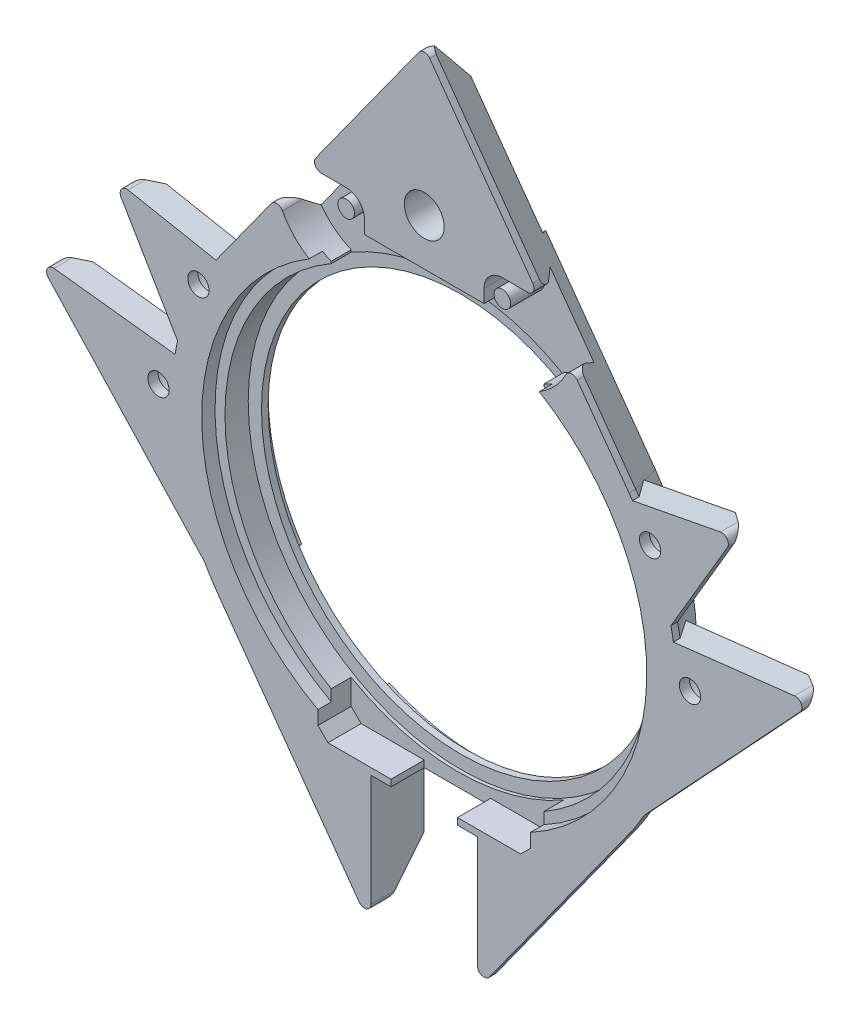
SolidWorks part; units mm, degrees
ref_plane "Спереди" through (0, 0, 0) normal (0, 0, 1) x (1, 0, 0)
ref_plane "Сверху" through (0, 0, 0) normal (0, 1, 0) x (1, 0, 0)
ref_plane "Справа" through (0, 0, 0) normal (1, 0, 0) x (0, 0, -1)
sketch "Эскиз1" plane through (0, 0, 0) normal (0, 0, 1) x (1, 0, 0)
  line L8 (0, 65) -> (30.8298, 22.2154)
  line L9 (0, -65) -> (30.8298, -22.2154)
  line L10 (-30.8298, 22.2154) -> (0, 65)
  line L11 (-30.8298, -22.2154) -> (0, -65)
  circle A0 centre (0, 0) radius 30
  arc A2 (30.8298, 22.2154) -> (30.8298, -22.2154) centre (0, 0) cw
  arc A3 (-30.8298, 22.2154) -> (-30.8298, -22.2154) centre (0, 0) ccw
  arc A10 (-0.8113, -63.8741) -> (0.8113, -63.8741) centre (0, -63.2895) ccw
  arc A11 (0.8113, 63.8741) -> (-0.8113, 63.8741) centre (0, 63.2895) ccw
  point P5 (0, -65)
  point P9 (0, 65)
  point P15 (0, 65)
  point P16 (0, -65)
  dimension "D1" = 60
  dimension "D2" = 2
  dimension "D7" = 38
  dimension "D8" = 65
  dimension "D9" = 65
extrude "Бобышка-Вытянуть1" add sketch "Эскиз1" along normal blind 8
chamfer "Фаска12" distance 7 distance2 5 6 edges at (-15.8206, -43.0447, 0) (15.8206, -43.0447, 0) (38, 0, 0) (-38, 0, 0) (-15.8206, 43.0447, 0) (15.8206, 43.0447, 0) first distance on face at (-15.8206, -43.0447, 4) first distance on face at (15.8206, -43.0447, 4) first distance on face at (34.4149, 0, 4) first distance on face at (-34.4149, 0, 4) first distance on face at (-15.8206, 43.0447, 4) first distance on face at (15.8206, 43.0447, 4)
sketch "Эскиз11" plane through (0, 0, 0) normal (0, 0, -1) x (-1, 0, 0)
  circle A0 centre (0, 0) radius 31.5
  circle A2 centre (0, 0) radius 30 construction
  dimension "D1" = 1.5
extrude "Вырез-Вытянуть1" cut sketch "Эскиз11" against normal blind 1.5
sketch "Эскиз17" plane through (0, 0, 8) normal (0, 0, -1) x (-1, 0, 0)
  line L0 (31.4303, -20.4545) -> (58.4303, 8.5455)
  line L1 (58.4303, 8.5455) -> (32.5307, 5.5455)
  line L3 (36.7549, 7.438) -> (46.7549, 24.438)
  line L4 (46.7549, 24.438) -> (25.9092, 20.438)
  line L5 (27.6586, -18) -> (31.4303, -20.4545)
  line L6 (36.7549, 7.438) -> (32.3444, 6.5455)
  line L7 (-32.3444, 6.5455) -> (-36.7549, 7.438)
  line L8 (-36.7549, 7.438) -> (-46.7549, 24.438)
  line L9 (-46.7549, 24.438) -> (-25.9092, 20.438)
  line L10 (-32.5307, 5.5455) -> (-58.4303, 8.5455)
  line L11 (-58.4303, 8.5455) -> (-31.4303, -20.4545)
  line L12 (-31.4303, -20.4545) -> (-27.6586, -18)
  arc A1 (-44.5835, 24.0214) -> (-45.6339, 22.5322) centre (-44.772, 23.0393) ccw
  circle A3 centre (0, 0) radius 33
  arc A6 (45.6339, 22.5322) -> (44.5835, 24.0214) centre (44.772, 23.0393) ccw
  arc A7 (56.5801, 6.5583) -> (55.7332, 8.233) centre (55.8482, 7.2397) ccw
  arc A8 (-55.7332, 8.233) -> (-56.5801, 6.5583) centre (-55.8482, 7.2397) ccw
  line M61 (0.8113, 63.8741) -> (30.8298, 22.2154)
  arc M62 (30.8298, 22.2154) -> (30.8298, -22.2154) centre (0, 0) cw
  line M64 (-0.8113, -63.8741) -> (-30.8298, -22.2154)
  arc M65 (-30.8298, -22.2154) -> (-30.8298, 22.2154) centre (0, 0) cw
  dimension "D11" = 66
  dimension "D3" = 2
  dimension "D2" = 18
  dimension "D8" = 1
  dimension "D12" = 4.5
  dimension "D13" = 4
  dimension "D14" = 3
  dimension "D15" = 29
  dimension "D16" = 17
  dimension "D17" = 27
  dimension "D18" = 10
extrude "Бобышка-Вытянуть5" add sketch "Эскиз17" along normal blind 4 separate body contours L8 L9 M65 | L9 A3 L7 M65 | L11 L10 M65 M64 | L10 A3 L12 L11 M64 M65 | L5 A3 L1 M62 | L5 L1 L0 M62 | L3 L6 L4 M62 M61 | L6 A3 L4 M61 M62
chamfer "Фаска13" distance 3 1 edges at (-44.0052, -6.9481, 4)
chamfer "Фаска14" distance 3 1 edges at (44.0052, -6.9481, 4)
chamfer "Фаска15" distance 3 1 edges at (41.1944, 14.9851, 4)
chamfer "Фаска16" distance 3 1 edges at (-41.1944, 14.9851, 4)
combine bodies "Соединить2" operation type add bodies to combine 136 135 134 137 113
sketch "Эскиз36" plane through (0, 0, 8) normal (0, 0, 1) x (1, 0, 0)
  line L0 (-16, 36) -> (16, -34) construction
  line L1 (-16, 36) -> (16, 36)
  line L2 (-16, 36) -> (-16, -34)
  line L3 (-16, -34) -> (16, -34)
  line L4 (16, 36) -> (16, -34)
  line L9 (16, 36) -> (-16, -34) construction
  point P6 (0, 1)
  dimension "D1" = 70
  dimension "D2" = 1
  dimension "D3" = 32
extrude "Вырез-Вытянуть17" cut sketch "Эскиз36" against normal offset from surface (5 mm away) 1.5 up to face at (-30, 0, 1.5)
sketch "Эскиз13" plane through (0, 0, 8) normal (0, 0, 1) x (1, 0, 0)
  line L0 (-16, -34) -> (16, -34) construction
  line L1 (-8, -34) -> (8, -34)
  line L2 (-8, -34) -> (-8, -65)
  line L3 (-8, -65) -> (8, -65)
  line L4 (8, -34) -> (8, -65)
  point P5 (0, -65)
  dimension "D1" = 16
  dimension "D2" = 65
extrude "Вырез-Вытянуть2" cut sketch "Эскиз13" against normal through all
sketch "Эскиз24" plane through (0, 0, 8) normal (0, 0, 1) x (1, 0, 0)
  circle A2 centre (0, 0) radius 32
  circle A3 centre (0, 0) radius 30 construction
  dimension "D1" = 2
extrude "Вырез-Вытянуть8" cut sketch "Эскиз24" against normal offset from surface (5.5 mm away) 1 up to face at (-30, 0, 1.5)
chamfer "Фаска20" distance 2.5 angle 45 4 edges at (-16, 36, 5.5) (16, 36, 5.5) (-16, -34, 5.5) (16, -34, 5.5)
sketch "Эскиз37" plane through (0, 0, 8) normal (0, 0, 1) x (1, 0, 0)
  line L1 (16, 27.7128) -> (16, 33.5) construction
  line L5 (13.5, 36) -> (-13.5, 36) construction
  line L6 (-11.75, 40.75) -> (-22.25, 40.75)
  line L8 (-9, 38) -> (-9, 27.5)
  line L13 (9, 38) -> (9, 27.5)
  line L14 (11.75, 40.75) -> (22.25, 40.75)
  line L16 (-16, 33.5) -> (-16, 27.7128) construction
  circle A0 centre (11.75, 38) radius 1.25
  circle A1 centre (11.75, 38) radius 1.5
  circle A5 centre (11.75, 38) radius 2.5
  circle A6 centre (11.75, 38) radius 2.75
  arc A7 (22.25, 40.75) -> (9, 27.5) centre (11.75, 38) cw
  circle A12 centre (-11.75, 38) radius 1.25
  circle A13 centre (-11.75, 38) radius 1.5
  circle A14 centre (-11.75, 38) radius 2.5
  circle A15 centre (-11.75, 38) radius 2.75
  arc A16 (-9, 27.5) -> (-22.25, 40.75) centre (-11.75, 38) cw
  line M6 (-16, 27.7128) -> (-16, 33.5)
  line M7 (-16, 33.5) -> (-13.5, 36)
  line M8 (-13.5, 36) -> (13.5, 36)
  line M9 (13.5, 36) -> (16, 33.5)
  line M10 (16, 33.5) -> (16, 27.7128)
  line M26 (30.8298, 22.2154) -> (0.8113, 63.8741)
  line M28 (-0.8113, 63.8741) -> (-30.8298, 22.2154)
  dimension "D3" = 5
  dimension "D4" = 5.5
  dimension "D1" = 2.5
  dimension "D2" = 3
  dimension "D8" = 7
  dimension "D5" = 7
  dimension "D6" = 2
  dimension "D7" = 10.5
extrude "Вырез-Вытянуть19" cut sketch "Эскиз37" against normal up to surface (5 mm away) contours A7 L14 A6 M26 M9 M10 | A7 A6 L13 M10 M9 M8 | A6 L13 M8 | A5 A1 M9 M8 | A1 A0 | A5 M8 M9 | A6 A5 M8 M9 | A6 A5 M8 M9 | A16 A15 L6 M6 M7 M28 | A15 A14 M7 M8 | A14 A13 M8 | A13 A12 | A15 L8 M8 up to face at (0, 33.1188, 3)
sketch "Эскиз25" plane through (0, 0, 4) normal (0, 0, -1) x (-1, 0, 0)
  line L0 (-34, 17) -> (34, 17) construction
  line L1 (-40, 1) -> (40, 1) construction
  circle A0 centre (-34, 17) radius 3.5
  circle A1 centre (-40, 1) radius 3.5
  circle A2 centre (34, 17) radius 3.5
  circle A3 centre (40, 1) radius 3.5
  point P0 (-34, 17)
  point P1 (34, 17)
  point P2 (40, 1)
  point P3 (-40, 1)
  point P8 (0, 17)
  point P9 (0, 1)
  dimension "D5" = 7
  dimension "D1" = 40
  dimension "D2" = 34
  dimension "D3" = 1
  dimension "D4" = 17
extrude "Вырез-Вытянуть9" cut sketch "Эскиз25" against normal blind 2.5 and the other way through all
hole_wizard "Диаметр отверстия Ø3.2 (3.2)1" positions "Эскиз26" profile "Эскиз27" hole size "Ø3.2" standard "DIN" end condition through all
sketch "Эскиз26" plane through (0, 0, 6.5) normal (0, 0, -1) x (-1, 0, 0)
  point P0 (-34, 17)
  point P3 (-40, 1)
  point P6 (34, 17)
  point P9 (40, 1)
sketch "Эскиз27" plane through (34, 17, 6.5) normal (1, 0, 0) x (0, 1, 0)
  line L0 (0, 0) -> (0, 1.5)
  line L1 (0, 1.5) -> (1.6, 1.5)
  line L2 (1.6, 1.5) -> (1.6, 0)
  line L5 (1.6, 0) -> (0, 0)
  line L11 (0, -6.35) -> (0, 107.95) construction
  dimension "Диаметр сквозного отверстия" = 3.2
  dimension "Глубина сквозного отверстия" = 1.5
sketch "Эскиз33" plane through (0, 0, 0) normal (0, 0, -1) x (-1, 0, 0)
  line L0 (-14.3954, 45.0225) -> (0, 65)
  line L1 (0, 65) -> (14.3954, 45.0225)
  line L4 (0.8113, 63.8741) -> (17.4741, 40.75) construction
  line L5 (-17.4741, 40.75) -> (-0.8113, 63.8741) construction
  arc A0 (1.5, 31.4643) -> (-1.5, 31.4643) centre (0, 0) ccw
  arc A1 (1.5, 31.4643) -> (14.3954, 45.0225) centre (32.3857, 15) cw
  arc A2 (-1.5, 31.4643) -> (-14.3954, 45.0225) centre (-32.3857, 15) ccw
  circle A3 centre (0, 0) radius 31.5 construction
  point P5 (0, 31.5)
  dimension "D3" = 35
  dimension "D1" = 3
  dimension "D4" = 15
extrude "Вырез-Вытянуть14" cut sketch "Эскиз33" against normal blind 1
sketch "Эскиз34" plane through (0, 0, 0) normal (0, 0, -1) x (-1, 0, 0)
  circle A0 centre (0, -40) radius 17.5
  circle A1 centre (0, -40) radius 35
  dimension "D1" = 35
  dimension "D2" = 70
  dimension "D3" = 40
extrude "Вырез-Вытянуть15" cut sketch "Эскиз34" against normal blind 1
fillet "Скругление1" radius 1 2 edges at (-8, -53.8979, 7.5) (8, -53.8979, 7.5)
sketch "Эскиз38" plane through (0, 0, 3) normal (0, 0, 1) x (1, 0, 0)
  line L0 (-8, -34) -> (8, -34) construction
  line L1 (-14.5, -33) -> (14.5, -33)
  line L2 (-14.5, -33) -> (-14.5, -34)
  line L3 (-14.5, -34) -> (14.5, -34)
  line L4 (14.5, -33) -> (14.5, -34)
  line L5 (13.5, -34) -> (16, -31.5) construction
  line L6 (-16, -31.5) -> (-13.5, -34) construction
  line L7 (-5, -33) -> (-5, -34)
  line L8 (5, -33) -> (5, -34)
  line M6 (-16, -31.5) -> (-13.5, -34)
  line M7 (-13.5, -34) -> (-8, -34)
  line M8 (-8, -34) -> (8, -34)
  line M9 (8, -34) -> (13.5, -34)
  line M10 (13.5, -34) -> (16, -31.5)
  dimension "D1" = 1
  dimension "D2" = 10
  dimension "D3" = 5
extrude "Бобышка-Вытянуть6" add sketch "Эскиз38" along normal up to surface (5 mm away) contours L7 L1 M6 M7 M8 | L1 L8 M8 M9 M10 up to face at (-35.6, 17, 8)
sketch "Эскиз39" plane through (0, 0, 1) normal (0, 0, -1) x (-1, 0, 0)
  circle A0 centre (0, 43) radius 3
  dimension "D2" = 6
  dimension "D1" = 43
extrude "Вырез-Вытянуть20" cut sketch "Эскиз39" against normal through all both and the other way through all
chamfer "Фаска21" distance 2 angle 45 1 edges at (3, 43, 1)
sketch "Эскиз40" plane through (0, 0, 8) normal (0, 0, 1) x (1, 0, 0)
  line L0 (-15.9272, -29.4716) -> (15.9272, -29.4716)
  circle A0 centre (0, 0) radius 33.5
  arc A1 (16, -27.7128) -> (16, 27.7128) centre (0, 0) ccw construction
  circle A2 centre (0, 0) radius 32
  arc M7 (-16, -27.7128) -> (-16, 27.7128) centre (0, 0) cw
  line M8 (-16, 27.7128) -> (-16, 28.0125)
  arc M9 (-16, 28.0125) -> (-22.0093, 34.4562) centre (-11.75, 38) cw
  dimension "D1" = 1.5
extrude "Вырез-Вытянуть21" cut sketch "Эскиз40" against normal blind 2 contours A0 L0 M9 M7 M8 | A2 L0 A0 M9 M8
fillet "Скругление2" radius 1 4 edges at (17.4741, 40.75, 7.5) (22.0093, 34.4562, 7.5) (-22.0093, 34.4562, 7.5) (-17.4741, 40.75, 7.5)
